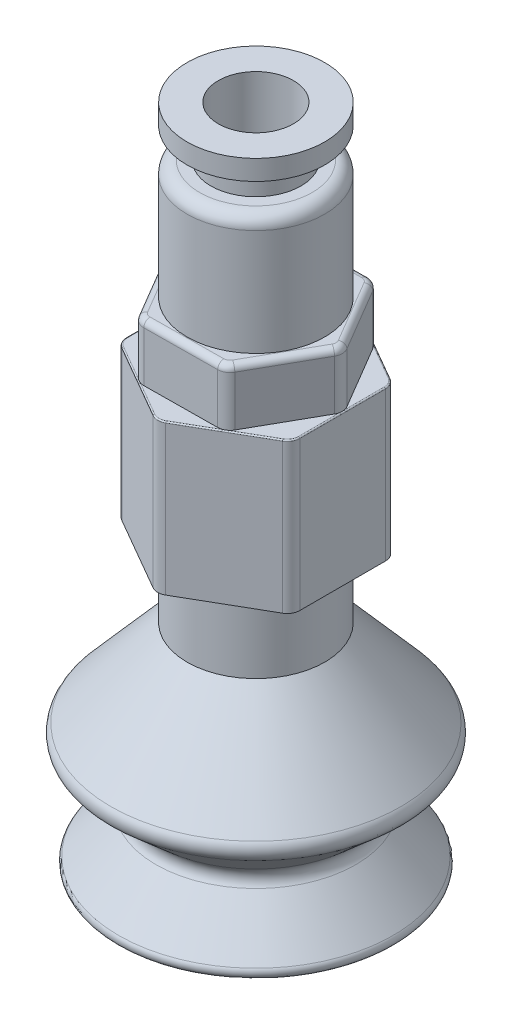
SolidWorks part; units mm, degrees
ref_plane "Plan de face" through (0, 0, 0) normal (0, 0, 1) x (1, 0, 0)
ref_plane "Plan de dessus" through (0, 0, 0) normal (0, 1, 0) x (1, 0, 0)
ref_plane "Plan de droite" through (0, 0, 0) normal (1, 0, 0) x (0, 0, -1)
sketch "Esquisse1" plane through (0, 0, 0) normal (0, 0, 1) x (1, 0, 0)
  line L0 (0, 71.4749) -> (0, 0) construction
  line L1 (0, 59.9654) -> (3, 59.9654)
  line L2 (3, 59.9654) -> (3, 80.3294)
  line L3 (3, 80.3294) -> (5.5, 80.3294)
  line L4 (5.5, 80.3294) -> (5.5, 78.7294)
  line L5 (5.5, 78.7294) -> (3.9, 78.7294)
  line L6 (3.9, 78.7294) -> (3.9, 78.1294)
  line L7 (3.9, 78.1294) -> (3.5993, 78.1294)
  line L8 (3.5993, 78.1294) -> (3.5993, 76.3294)
  line L9 (3.5993, 76.3294) -> (5.5, 76.3294)
  line L10 (5.5, 76.3294) -> (5.5, 66.8294)
  line L11 (5.5, 66.8294) -> (7, 66.8294)
  line L12 (7, 66.8294) -> (7, 62.3294)
  line L13 (7, 62.3294) -> (8, 62.3294)
  line L14 (8, 62.3294) -> (8, 50.3294)
  line L15 (8, 50.3294) -> (5.5, 50.3294)
  line L16 (5.5, 50.3294) -> (5.5, 44.3294)
  line L17 (5.5, 44.3294) -> (12.25, 36.6294)
  line L18 (12.25, 36.6294) -> (7.329, 32.3156)
  line L19 (7.329, 32.3156) -> (11.7, 27.3294)
  line L20 (11.7, 27.3294) -> (9.371, 27.3294)
  line L21 (9.371, 27.3294) -> (5, 32.3156)
  line L22 (5, 32.3156) -> (9.921, 36.6294)
  line L23 (9.921, 36.6294) -> (3.171, 44.3294)
  line L24 (3.171, 44.3294) -> (3.171, 50.3294)
  line L25 (3.171, 50.3294) -> (0, 50.3294)
  line L26 (9.921, 36.6294) -> (12.25, 36.6294) construction
  line L27 (3.171, 44.3294) -> (5.5, 44.3294) construction
  line L28 (7.329, 32.3156) -> (5, 32.3156) construction
  line L29 (0, 59.9654) -> (0, 50.3294)
  dimension "D1" = 5.5
  dimension "D2" = 0.9
  dimension "D3" = 1.6
  dimension "D4" = 0.6
  dimension "D5" = 5.5
  dimension "D6" = 30
  dimension "D7" = 12
  dimension "D8" = 1.8
  dimension "D9" = 9.5
  dimension "D10" = 16
  dimension "D11" = 14
  dimension "D12" = 6
  dimension "D13" = 11
  dimension "D14" = 24.5
  dimension "D15" = 53
  dimension "D16" = 10
  dimension "D17" = 6
  dimension "D18" = 7.7
  dimension "D19" = 23.4
revolve "Révolution1" add sketch "Esquisse1" angle 360 about L0
fillet "Congé1" radius 1 3 edges at (0, 36.6294, 12.25) (0, 32.3156, 7.329) (0, 76.3294, 5.5)
sketch "Esquisse2" plane through (0, 62.3294, 0) normal (0, 1, 0) x (1, 0, 0)
  line L1 (0, 8) -> (-6.9282, 4)
  line L2 (-6.9282, 4) -> (-6.9282, -4)
  line L3 (-6.9282, -4) -> (0, -8)
  line L4 (0, -8) -> (6.9282, -4)
  line L5 (6.9282, -4) -> (6.9282, 4)
  line L6 (6.9282, 4) -> (0, 8)
  circle A0 centre (0, 0) radius 6.9282 construction
extrude "Enlèv. de mat.-Extru.-Mince1" cut sketch "Esquisse2" against normal blind 13 thin thin type one direction wall 20
sketch "Esquisse3" plane through (0, 66.8294, 0) normal (0, 1, 0) x (1, 0, 0)
  line L1 (-3.5581, 6.0282) -> (-6.9997, -0.0673)
  line L2 (-6.9997, -0.0673) -> (-3.4416, -6.0955)
  line L3 (-3.4416, -6.0955) -> (3.5581, -6.0282)
  line L4 (3.5581, -6.0282) -> (6.9997, 0.0673)
  line L5 (6.9997, 0.0673) -> (3.4416, 6.0955)
  line L6 (3.4416, 6.0955) -> (-3.5581, 6.0282)
  circle A0 centre (0, 0) radius 6.0622 construction
extrude "Enlèv. de mat.-Extru.-Mince2" cut sketch "Esquisse3" against normal blind 4.5 thin thin type one direction wall 20
fillet "Congé2" radius 1 12 edges at (0, 56.3294, -8) (-3.5581, 64.5794, -6.0282) (3.4416, 64.5794, -6.0955) (6.9997, 64.5794, -0.0673) (6.9282, 56.3294, -4) (6.9282, 56.3294, 4) (3.5581, 64.5794, 6.0282) (0, 56.3294, 8) (-3.4416, 64.5794, 6.0955) (-6.9997, 64.5794, 0.0673) (-6.9282, 56.3294, -4) (-6.9282, 56.3294, 4)
fillet "Congé3" radius 0.5 13 edges at (-3.3655, 66.8294, 5.9608) (-5.2206, 66.8294, 3.0814) (-6.845, 66.8294, 0.0658) (-5.2789, 66.8294, -2.9805) (-3.4795, 66.8294, -5.895) (-0.0583, 66.8294, -6.0619) (3.3655, 66.8294, -5.9608) (5.2206, 66.8294, -3.0814) (6.845, 66.8294, -0.0658) (5.2789, 66.8294, 2.9805) (3.4795, 66.8294, 5.895) (0.0583, 66.8294, 6.0619) (0, 27.3294, 11.7)
fillet "Congé4" radius 0.1 12 edges at (-3.4641, 62.3294, 6) (-6.7942, 62.3294, 3.9226) (-6.9282, 62.3294, 0) (-6.7942, 62.3294, -3.9226) (-3.4641, 62.3294, -6) (0, 62.3294, -7.8453) (3.4641, 62.3294, -6) (6.7942, 62.3294, -3.9226) (6.9282, 62.3294, 0) (6.7942, 62.3294, 3.9226) (3.4641, 62.3294, 6) (0, 62.3294, 7.8453)
